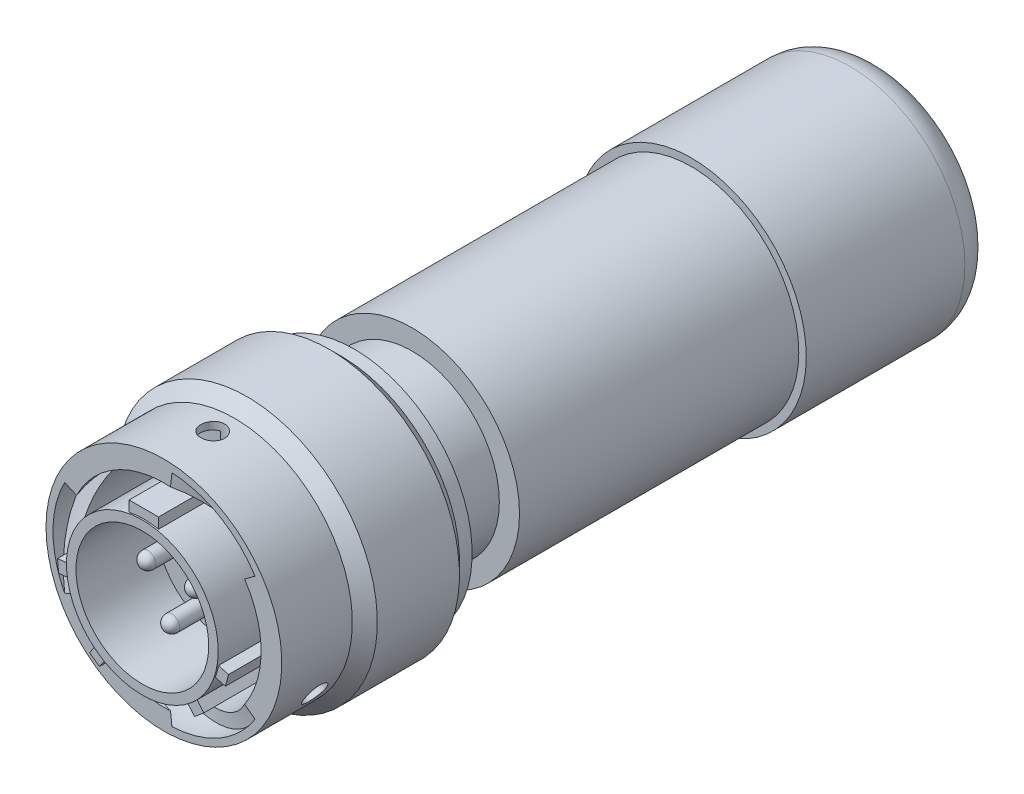
SolidWorks part; units mm, degrees
ref_plane "Front Plane" through (0, 0, 0) normal (0, 0, 1) x (1, 0, 0)
ref_plane "Top Plane" through (0, 0, 0) normal (0, 1, 0) x (1, 0, 0)
ref_plane "Right Plane" through (0, 0, 0) normal (1, 0, 0) x (0, 0, -1)
sketch "Sketch1" plane through (0, 0, 0) normal (1, 0, 0) x (0, 0, -1)
  line L0 (0, 0) -> (74, 0) construction
  line L1 (0, 13.05) -> (0, -13.05) construction
  line L2 (27, 10.75) -> (27, -10.75) construction
  line L3 (74, 11.5) -> (74, -11.5) construction
  line L4 (0, 9.7282) -> (0, -9.7282) construction
  line L6 (0, 6.6421) -> (0, -6.6421) construction
  line L7 (0, 7.5946) -> (0, -7.5946) construction
  line L8 (7.9502, 6.5532) -> (7.9502, -6.5532) construction
  line L10 (0, 11.8) -> (0, -11.8) construction
  line L13 (0, 0) -> (7.9502, 0) construction
  line L14 (32.5, 8.7312) -> (32.5, -8.7312) construction
  line L15 (9.2202, 8.636) -> (9.2202, -8.636) construction
  line L16 (0, 11.1252) -> (0, -11.1252) construction
  line L17 (32.5, 8.7312) -> (31.4417, 8.7312) construction
  point P12 (0.1524, 0)
  point P14 (7.9502, 0)
  point P21 (2.159, 0)
  point P22 (5.842, 0)
  point P25 (30.722, 0)
  point P29 (27, 0)
  point P30 (23.356, 0)
  point P34 (32.5, 0)
  point P42 (9.2202, 0)
  dimension "D1" = 7.366
sketch "Sketch2" plane through (0, 0, 0) normal (0, 0, 1) x (1, 0, 0)
  circle A0 centre (0, 0) radius 7.5946 construction
  circle A1 centre (0, 0) radius 8.636 construction
  circle A2 centre (0, 0) radius 13.05 construction
  circle A3 centre (0, 0) radius 11.1252 construction
sketch "Sketch3" plane through (0, 0, 0) normal (1, 0, 0) x (0, 0, -1)
  line L0 (0, 0) -> (74, 0) construction
  line L1 (9.7282, 8.636) -> (9.7282, 7.6729)
  line L2 (0, 7.5946) -> (9.2202, 7.5946)
  line L3 (0, 7.5946) -> (0, 6.6421)
  line L4 (0, 6.6421) -> (32.5, 6.6421)
  line L5 (19.8, 7.6729) -> (20.8583, 8.7312)
  line L6 (9.7282, 7.6729) -> (19.8, 7.6729)
  line L7 (7.9502, 6.5532) -> (30.722, 6.5532)
  line L8 (7.9502, 6.5532) -> (7.9502, 0)
  line L9 (7.9502, 0) -> (30.722, 0)
  line L10 (30.722, 6.5532) -> (30.722, 0)
  line L11 (20.8583, 8.7312) -> (31.4417, 8.7312)
  line L12 (31.4417, 8.7312) -> (32.5, 7.6729)
  line L13 (31.4417, 8.7312) -> (32.5, 8.7312) construction
  line L14 (32.5, 8.7312) -> (32.5, 7.6729) construction
  line L15 (19.8, 7.6729) -> (19.8, 8.7312) construction
  line L16 (19.8, 8.7312) -> (20.8583, 8.7312) construction
  line L26 (32.5, 7.6729) -> (32.5, 6.6421)
  line L31 (9.7282, 8.636) -> (9.2202, 8.636)
  line L35 (9.2202, 8.636) -> (9.2202, 7.5946)
  dimension "D1" = 12.7
  dimension "D2" = 0.508
revolve "Revolve1" add sketch "Sketch3" angle 360 about L0
sketch "Sketch4" plane through (0, 0, 0) normal (0, 0, 1) x (1, 0, 0)
  line L0 (-1.4732, 8.5094) -> (1.4732, 8.5094)
  line L1 (0, 8.5094) -> (0, 0) construction
  line L2 (0, 0) -> (8.3209, -2.2296) construction
  line L3 (0, 0) -> (5.5373, -6.5991) construction
  line L4 (0, 0) -> (-4.9411, -7.0566) construction
  line L5 (0, 0) -> (-8.5817, -0.7508) construction
  line L6 (8.4787, -1.6408) -> (8.1632, -2.8184)
  line L7 (6.0042, -6.2072) -> (5.0703, -6.9909)
  line L8 (-4.4417, -7.4062) -> (-5.4404, -6.7069)
  line L9 (-8.5285, -1.3581) -> (-8.6348, -0.1435)
  line L10 (8.4787, -1.6408) -> (7.4699, -1.3705)
  line L11 (8.1632, -2.8184) -> (7.1544, -2.5481)
  line L12 (6.0042, -6.2072) -> (5.3329, -5.4072)
  line L13 (5.0703, -6.9909) -> (4.399, -6.1909)
  line L14 (-4.4417, -7.4062) -> (-3.8427, -6.5507)
  line L15 (-5.4404, -6.7069) -> (-4.8414, -5.8514)
  line L16 (-8.5285, -1.3581) -> (-7.4882, -1.2671)
  line L17 (-8.6348, -0.1435) -> (-7.5944, -0.0525)
  line L18 (-1.4732, 8.5094) -> (-1.4732, 7.4503)
  line L19 (1.4732, 8.5094) -> (1.4732, 7.4503)
  arc A0 (4.399, -6.1909) -> (5.3329, -5.4072) centre (0, 0) ccw
  arc A1 (7.1544, -2.5481) -> (7.4699, -1.3705) centre (0, 0) ccw
  circle A2 centre (0, 0) radius 7.5946 construction
  circle A3 centre (0, 0) radius 8.636 construction
  arc A4 (-4.8414, -5.8514) -> (-3.8427, -6.5507) centre (0, 0) ccw
  circle A5 centre (0, 0) radius 8.636 construction
  arc A6 (-7.5944, -0.0525) -> (-7.4882, -1.2671) centre (0, 0) ccw
  arc A7 (1.4732, 7.4503) -> (-1.4732, 7.4503) centre (0, 0) ccw
  dimension "D1" = 2.9464
  dimension "D2" = 105
  dimension "D3" = 140
  dimension "D4" = 215
  dimension "D5" = 265
  dimension "D6" = 1.2192
extrude "Boss-Extrude1" add sketch "Sketch4" against normal up to vertex (9.2202 mm away) from vertex up to point (0, 0, -9.2202) starting at point (0, 0, -0.1524)
sketch "Sketch5" plane through (0, 0, 0) normal (1, 0, 0) x (0, 0, -1)
  line L0 (32.5, 0) -> (0, 0) construction
  line L1 (2.159, 11.8) -> (2.159, 9.7282)
  line L3 (17.399, 9.7282) -> (17.399, 10.9982)
  line L4 (17.399, 10.9982) -> (21.209, 10.9982)
  line L5 (21.209, 10.9982) -> (21.209, 11.8)
  line L6 (2.159, 9.7282) -> (17.399, 9.7282)
  line L7 (2.159, 11.8) -> (9.2202, 11.8)
  line L8 (21.209, 11.8) -> (19.939, 11.8)
  line L9 (19.939, 11.8) -> (18.689, 13.05)
  line L10 (18.689, 13.05) -> (10.4702, 13.05)
  line L11 (10.4702, 13.05) -> (9.2202, 11.8)
  dimension "D2" = 1.27
  dimension "D5" = 45
  dimension "D1" = 3.81
  dimension "D3" = 19.05
  dimension "D4" = 45
  dimension "D6" = 1.27
revolve "Revolve2" add sketch "Sketch5" angle 360 about L0
sketch "Sketch6" plane through (0, 0, 0) normal (0, 1, 0) x (1, 0, 0)
  line L0 (0, 0) -> (0, 74) construction
  circle A0 centre (0, 7.0358) radius 1.1938
  dimension "D1" = 2.3876
extrude "Cut-Extrude1" cut sketch "Sketch6" along normal through all
sketch "Sketch7" plane through (0, 0, -2.159) normal (0, 0, 1) x (1, 0, 0)
  circle A0 centre (0, 0) radius 9.7282 construction
  circle A1 centre (0, 0) radius 9.7282
  point P3 (-9.7282, 0)
curve "Helix/Spiral1" pitch 19.5072 height 4.8768 radius 9.7282 centre (0, 0, -2.159) axis (0, 0, -1) start towards (1, 0, 0)
ref_plane "Plane2" through (-9.7282, 0, -2.159) normal (0, 0.9527, -0.304) x (-1, 0, 0)
sketch "Sketch8" plane through (-9.7282, 0, -2.159) normal (0, 0.9527, -0.304) x (-1, 0, 0)
  line L0 (-9.7282, 0) -> (0, 0) construction
  line L1 (0, 0) -> (1.3756, 0) construction
  line L2 (-0.0936, 1.3462) -> (1.2937, 1.3462)
  line L3 (1.3756, 0) -> (1.3756, 2.2663) construction
  line L4 (-0.0936, -1.3462) -> (1.2937, -1.3462)
  arc A0 (1.2937, -1.3462) -> (1.2937, 1.3462) centre (-9.7282, 0) ccw
  arc A1 (-0.0936, -1.3462) -> (-0.0936, 1.3462) centre (-9.7282, 0) ccw
  dimension "GG" = 2.6924
sweep "Cut-Sweep1" cut profiles "Sketch8" path "Helix/Spiral1" align with end faces yes
pattern_circular "CirPattern1" count 3 over 360 about axis through (0, 0, -32.5) along (0, 0, -1) of "Cut-Extrude1", "Cut-Sweep1"
sketch "Sketch9" plane through (0, 0, 0) normal (1, 0, 0) x (0, 0, -1)
  line L0 (27, 10.75) -> (27, 8.7312)
  line L1 (27, 8.7312) -> (70.825, 8.7312)
  line L2 (27, 10.75) -> (54.95, 10.75)
  line L3 (54.95, 11.5) -> (54.95, 10.75)
  line L4 (0, 0) -> (74, 0) construction
  line L5 (54.95, 11.5) -> (70.825, 11.5)
  line L6 (74, 5.15) -> (71.2313, 5.15)
  line L7 (71.2313, 5.15) -> (71.2313, 8.325)
  line L9 (74, 5.15) -> (74, 8.325)
  arc A0 (70.825, 11.5) -> (74, 8.325) centre (70.825, 8.325) cw
  arc A1 (71.2313, 8.325) -> (70.825, 8.7312) centre (70.825, 8.325) ccw
  point P11 (74, 11.5)
  dimension "D1" = 3.175
  dimension "D2" = 19.05
  dimension "D3" = 6.35
revolve "Revolve3" add sketch "Sketch9" angle 360 about L4
sketch "Sketch12-3P" plane through (0, 0, -7.9502) normal (0, 0, 1) x (1, 0, 0)
  circle A0 centre (2.3876, 1.4732) radius 0.7938
  circle A1 centre (0, -2.8194) radius 0.7938
  circle A2 centre (-2.3876, 1.4732) radius 0.7938
  dimension "D1" = 1.5875
  dimension "D2" = 2.3876
  dimension "D3" = 1.4732
  dimension "D4" = 0
  dimension "D5" = 2.8194
  dimension "D6" = 2.3876
  dimension "D7" = 1.4732
extrude "Boss-Extrude12-3P" add sketch "Sketch12-3P" along normal up to vertex (5.7912 mm away) up to point (0, 0, -2.159)
fillet "Fillet12-3P" radius 0.7937 3 edges at (3.1813, 1.4732, -2.159) (-1.5939, 1.4732, -2.159) (0.7938, -2.8194, -2.159)
sketch "Sketch12-xP" [suppressed] plane through (0, 0, -7.9502) normal (0, 0, 1) x (1, 0, 0)
  line L0 (-1.651, 3.9878) -> (1.651, 3.9878) construction
  line L1 (4.318, 0) -> (-4.318, 0) construction
  line L2 (3.048, -3.048) -> (-3.048, -3.048) construction
  line L3 (0, -4.318) -> (0, 0) construction
  line L4 (0, 1.1176) -> (0, 0) construction
  line L5 (0, 3.9878) -> (0, 0) construction
  line L6 (0, -3.048) -> (0, 1.1176) construction
  circle A0 centre (1.651, 3.9878) radius 0.7938
  circle A1 centre (4.318, 0) radius 0.7937
  circle A2 centre (3.048, -3.048) radius 0.7938
  circle A3 centre (0, -4.318) radius 0.7938
  circle A4 centre (-3.048, -3.048) radius 0.7938
  circle A5 centre (-4.318, 0) radius 0.7938
  circle A6 centre (-1.651, 3.9878) radius 0.7938
  circle A7 centre (0, 1.1176) radius 0.7938
  dimension "D1" = 1.5875
  dimension "D2" = 1.651
  dimension "D3" = 3.9878
  dimension "D5" = 3.048
  dimension "D6" = 3.048
  dimension "D7" = 4.318
  dimension "D8" = 1.1176
extrude "Boss-Extrude12-xP" [suppressed] add sketch "Sketch12-xP" along normal up to vertex up to point (0, 0, -2.159)
fillet "Fillet12-xP" [suppressed] radius 0.7937
sketch "Sketch12-10P" [suppressed] plane through (0, 0, -7.9502) normal (0, 0, 1) x (1, 0, 0)
  line L0 (3.302, 3.048) -> (-3.302, 3.048) construction
  line L1 (4.953, 0) -> (-4.953, 0) construction
  line L2 (3.302, 3.048) -> (3.302, -3.048) construction
  line L3 (3.302, -3.048) -> (-3.302, -3.048) construction
  line L4 (-3.302, -3.048) -> (-3.302, 3.048) construction
  line L5 (0, 3.048) -> (0, -3.048) construction
  line L6 (-1.651, 0) -> (1.651, 0) construction
  circle A0 centre (0, 3.048) radius 0.508
  circle A1 centre (3.302, 3.048) radius 0.508
  circle A2 centre (4.953, 0) radius 0.508
  circle A3 centre (3.302, -3.048) radius 0.508
  circle A4 centre (0, -3.048) radius 0.508
  circle A5 centre (-3.302, -3.048) radius 0.508
  circle A6 centre (-4.953, 0) radius 0.508
  circle A7 centre (-3.302, 3.048) radius 0.508
  circle A8 centre (1.651, 0) radius 0.508
  circle A9 centre (-1.651, 0) radius 0.508
  dimension "D1" = 1.016
  dimension "D2" = 3.048
  dimension "D3" = 4.953
  dimension "D5" = 3.302
  dimension "D4" = 1.651
extrude "Boss-Extrude12-10P" [suppressed] add sketch "Sketch12-10P" along normal up to vertex up to point (0, 0, -2.159)
fillet "Fillet12-10P" [suppressed] radius 0.508
equation "\"D3@Helix/Spiral1\" = \"N@Sketch1\" - \"D@Sketch1\" - \"E@Sketch1\" + ( \"D1@Sketch6\" / 2 ) "
equation "\"D1@Fillet12-3P\" = \"D1@Sketch12-3P\" / 2"
equation "\"D1@Fillet12-xP\" = \"D1@Sketch12-xP\" / 2"
equation "\"D1@Fillet12-10P\" = \"D1@Sketch12-10P\" / 2"
